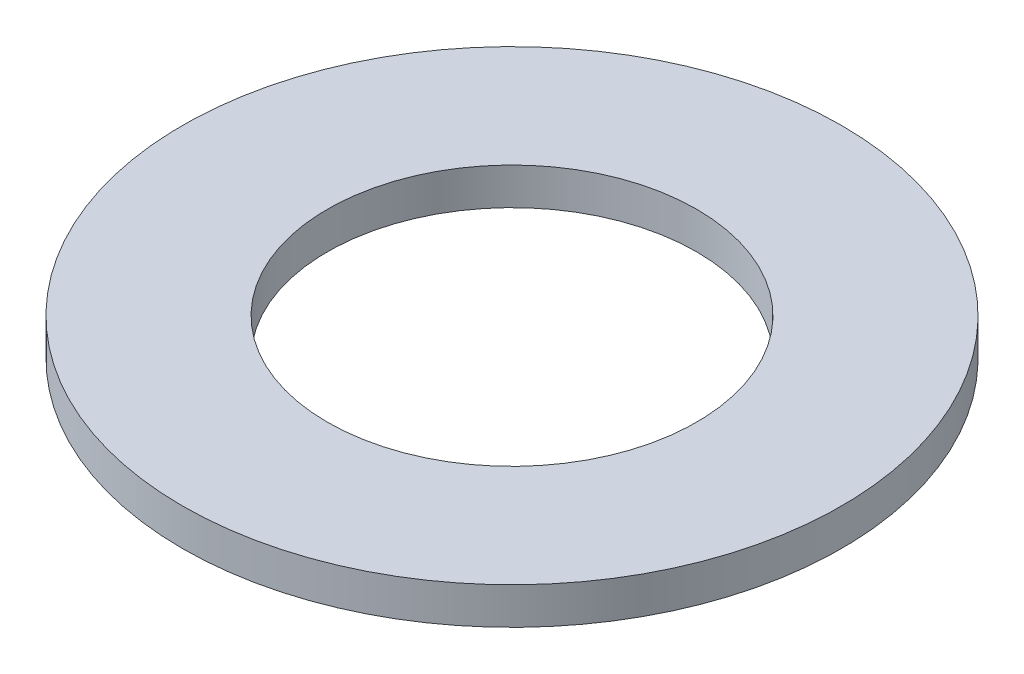
SolidWorks part; units mm, degrees
ref_plane "Front Plane" through (0, 0, 0) normal (0, 0, 1) x (1, 0, 0)
ref_plane "Top Plane" through (0, 0, 0) normal (0, 1, 0) x (1, 0, 0)
ref_plane "Right Plane" through (0, 0, 0) normal (1, 0, 0) x (0, 0, -1)
sketch "Sketch1" plane through (0, 0, 0) normal (0, 1, 0) x (1, 0, 0)
  circle A0 centre (0, 0) radius 62.5
  dimension "FLANGE_OD" = 125
extrude "Boss-Extrude1" add sketch "Sketch1" along normal blind 7
sketch "Sketch2" plane through (0, 0, 0) normal (0, 1, 0) x (1, 0, 0)
  circle A0 centre (0, 0) radius 35
  dimension "BORE_D" = 70
extrude "Cut-Extrude1" cut sketch "Sketch2" along normal through all
sketch "Sketch3" plane through (0, 7, 0) normal (0, 1, 0) x (1, 0, 0)
  circle A0 centre (0, 0) radius 25.7046 construction
  circle A1 centre (-25.7046, 0) radius 2.682
  dimension "BOLT_D" = 5.364
  dimension "BOLT_PCD" = 51.4092
extrude "Cut-Extrude2" cut sketch "Sketch3" against normal blind 6.2474 rebuild error yes
pattern_circular "CirPattern1" count 4 over 360 rebuild error yes
